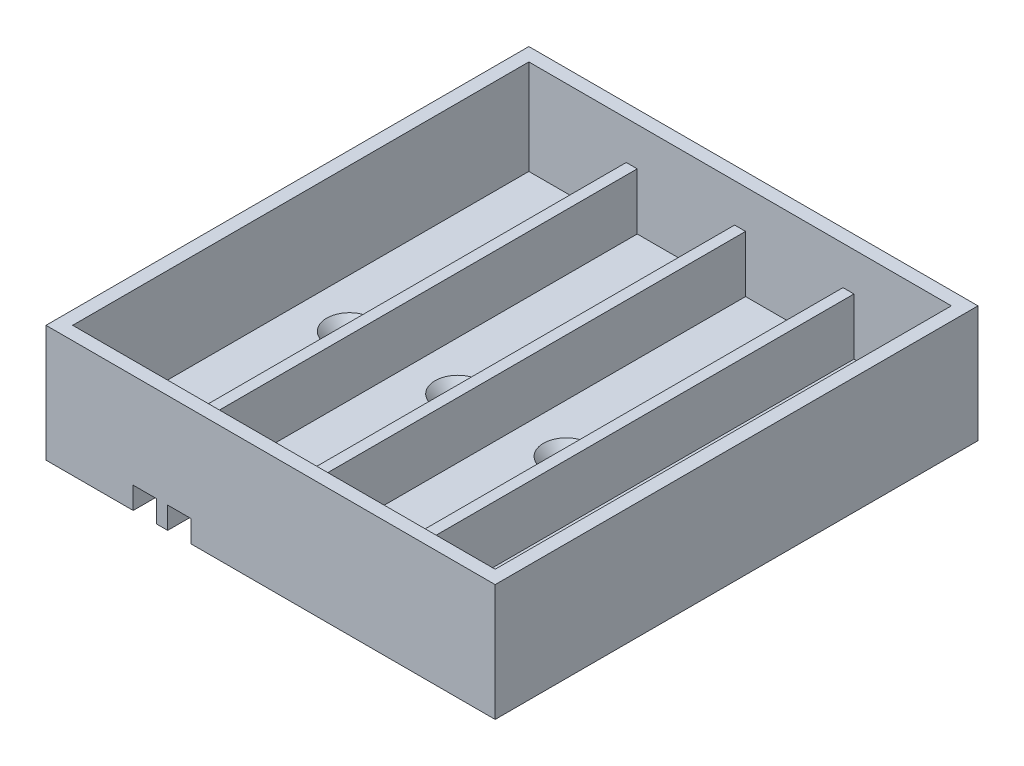
SolidWorks part; units mm, degrees
ref_plane "前视基准面" through (0, 0, 0) normal (0, 0, 1) x (1, 0, 0)
ref_plane "上视基准面" through (0, 0, 0) normal (0, 1, 0) x (1, 0, 0)
ref_plane "右视基准面" through (0, 0, 0) normal (1, 0, 0) x (0, 0, -1)
other "Configuration Table"
sketch "草图1" plane through (0, 0, 0) normal (0, 1, 0) x (1, 0, 0)
  line L0 (-26.95, 30.8) -> (-26.95, -30.8)
  line L1 (-28.65, -30.8) -> (28.65, -30.8)
  line L2 (-28.65, -30.8) -> (-28.65, 30.8)
  line L3 (-28.65, 30.8) -> (28.65, 30.8)
  line L4 (28.65, -30.8) -> (28.65, 30.8)
  line L5 (-28.65, -30.8) -> (28.65, 30.8) construction
  line L6 (-28.65, 30.8) -> (28.65, -30.8) construction
  line L39 (-17.525, -30.8) -> (-14.525, -30.8)
  line L40 (-17.525, -30.8) -> (-17.525, -24)
  line L41 (-17.525, -24) -> (-14.525, -24)
  line L42 (-14.525, -30.8) -> (-14.525, -24)
  line L43 (-13.125, -30.8) -> (-10.125, -30.8)
  line L44 (-13.125, -30.8) -> (-13.125, -24)
  line L45 (-13.125, -24) -> (-10.125, -24)
  line L46 (-10.125, -30.8) -> (-10.125, -24)
  line L47 (-14.525, 30.8) -> (-13.125, 30.8)
  line L48 (-14.525, 30.8) -> (-14.525, -30.8)
  line L49 (-14.525, -30.8) -> (-13.125, -30.8)
  line L50 (-13.125, 30.8) -> (-13.125, -30.8)
  line L55 (13.125, 30.8) -> (14.525, 30.8)
  line L56 (13.125, 30.8) -> (13.125, -30.8)
  line L57 (13.125, -30.8) -> (14.525, -30.8)
  line L58 (14.525, 30.8) -> (14.525, -30.8)
  line L59 (26.95, 30.8) -> (26.95, -30.8)
  line L60 (-26.95, 0) -> (-14.525, 0)
  line L61 (-13.125, 0) -> (-0.7, 0)
  line L62 (0.7, 0) -> (13.125, 0)
  line L63 (14.525, 0) -> (26.95, 0)
  line L65 (-0.7, 30.8) -> (0.7, 30.8)
  line L66 (-0.7, 30.8) -> (-0.7, -30.8)
  line L67 (-0.7, -30.8) -> (0.7, -30.8)
  line L68 (0.7, 30.8) -> (0.7, -30.8)
  circle A0 centre (-20.7375, 0) radius 1.9
  circle A1 centre (-6.9125, 0) radius 1.9
  circle A2 centre (6.9125, 0) radius 1.9
  circle A3 centre (20.7375, 0) radius 1.9
  point P13 (-14.525, -27.4)
  dimension "D1" = 61.6
  dimension "D2" = 3
  dimension "D7" = 1.4
  dimension "D5" = 1.4
  dimension "D6" = 6.8
  dimension "D10" = 3.8
  dimension "D3" = 57.3
  dimension "D8" = 1.7
  dimension "D9" = 1.7
extrude "凸台-拉伸1" add sketch "草图1" along normal blind 2.8 contours L2 L3 L4 L1
extrude "拉伸-薄壁1" add sketch "草图1<11>" along normal blind 14.9 thin contours L2 L3 L4 L1 thin type one direction reverse wall 1.7
sketch "草图1<11>" plane through (0, 0, 0) normal (0, 1, 0) x (1, 0, 0) same geometry as "草图1"
extrude "切除-拉伸1" cut sketch "草图1<13>" along normal up to surface (2.8 mm away) contours L40 L41 L42 L39 | L44 L45 L46 L43 up to face at (0, 2.8, 0)
sketch "草图1<13>" plane through (0, 0, 0) normal (0, 1, 0) x (1, 0, 0) same geometry as "草图1"
extrude "凸台-拉伸2" add sketch "草图1<14>" along normal blind 10 contours L48 L49 L50 L47 | L66 L67 L68 L65 | L56 L57 L58 L55
sketch "草图1<14>" plane through (0, 0, 0) normal (0, 1, 0) x (1, 0, 0) same geometry as "草图1"
extrude "切除-拉伸2" cut sketch "草图1<15>" along normal through all contours A0 | A1 | A2 | A3
sketch "草图1<15>" plane through (0, 0, 0) normal (0, 1, 0) x (1, 0, 0) same geometry as "草图1"
chamfer "倒角1" distance 1 angle 45 4 edges at (-20.7375, 2.8, 1.9) (-6.9125, 2.8, 1.9) (6.9125, 2.8, 1.9) (20.7375, 2.8, 1.9)
